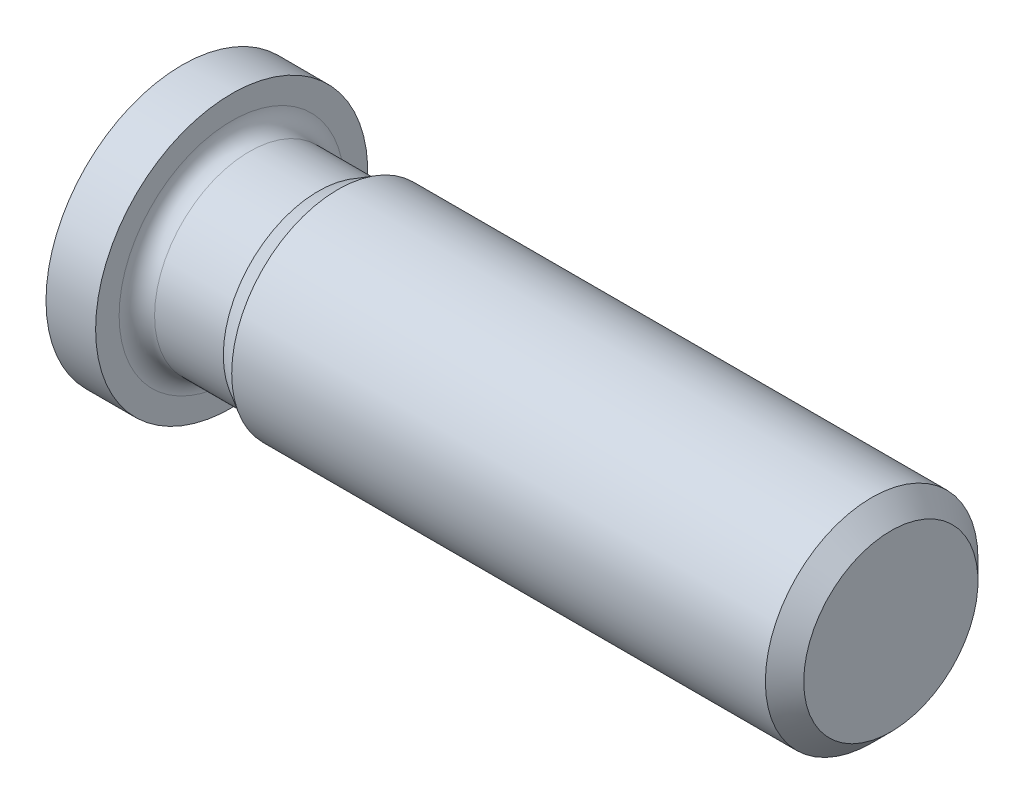
SolidWorks part; units mm, degrees
ref_plane "Front" through (0, 0, 0) normal (0, 0, 1) x (1, 0, 0)
ref_plane "Top" through (0, 0, 0) normal (0, 1, 0) x (1, 0, 0)
ref_plane "Right" through (0, 0, 0) normal (1, 0, 0) x (0, 0, -1)
sketch "Sketch1" plane through (0, 0, 0) normal (0, 0, 1) x (1, 0, 0)
  line L0 (0, 0) -> (22.7419, 0) construction
  line L1 (0, 0) -> (0, 0.44)
  line L2 (0, 0.44) -> (0.83, 0.9192)
  line L3 (0.83, 0.9192) -> (1.137, 3.84)
  line L4 (1.137, 3.84) -> (2.537, 3.84)
  line L5 (3.037, 3) -> (5.537, 3) construction
  line L6 (21.137, 3) -> (21.137, 0)
  line L7 (21.137, 0) -> (0, 0)
  line L8 (1.137, 3.84) -> (1.137, -8.0526) construction
  line L9 (2.537, 3.84) -> (2.537, 3.1765)
  line L10 (5.537, 3) -> (21.137, 3)
  line L11 (5.537, 3) -> (4.9767, 2.6765)
  line L12 (4.9767, 2.6765) -> (3.037, 2.6765)
  arc A0 (3.037, 2.6765) -> (2.537, 3.1765) centre (3.037, 3.1765) cw
  dimension "D5" = 0.5
  dimension "D3" = 6
  dimension "D4" = 30
  dimension "a" = 3
  dimension "d" = 6
  dimension "D6" = 5.353
revolve "Base" add sketch "Sketch1" angle 360 about L0
cosmetic thread "ThreadCosmetic1" [suppressed] parameters "D1"=15.6, "D2"=4.917
chamfer "EndChamfer" distance 0.5415 angle 45 1 edges at (21.137, 0, 3)
ref_plane "Plane1" through (4.037, 0, 0) normal (1, 0, 0) x (0, 0, -1)
sketch "Sketch2" plane through (0, 0, 0) normal (0, 0, 1) x (1, 0, 0)
  line L0 (20.5955, 2.531) -> (20.8662, 3)
  line L1 (20.8662, 3) -> (20.8662, 3.5)
  line L2 (20.8662, 3.5) -> (20.3247, 3.5)
  line L3 (20.3247, 3.5) -> (20.3247, 3)
  line L4 (20.3247, 3) -> (20.5955, 2.531)
  line L5 (0, 0) -> (22.4926, 0) construction
  line L7 (20.5955, 3) -> (20.5955, -3) construction
  dimension "D1" = 60
  dimension "D2" = 60
  dimension "D3" = 0.5
  dimension "D4" = 0.5415
  dimension "D5" = 6
revolve "Cut-Revolve10" [suppressed] cut sketch "Sketch2" angle 360 about L5
pattern_linear "LPattern10" [suppressed] count 24 spacing 0.6498 along (-1, 0, 0) of bodies 102
equation "\"D1@ThreadCosmetic1\" = \"l@Sketch1\" - \"h@Sketch1\" -\"a@Sketch1\""
equation "\"D1@EndChamfer\" =  ( \"d@Sketch1\" - \"D2@ThreadCosmetic1\" )  / 2"
equation "\"D5@Sketch2\" = \"d@Sketch1\""
equation "\"D4@Sketch2\" = (  \"d@Sketch1\" - \"D2@ThreadCosmetic1\" )  / 2"
equation "\"D3@LPattern10\" = \"D4@Sketch2\" * 1.2"
equation "\"D1@LPattern10\" = \"D1@ThreadCosmetic1\" / \"D3@LPattern10\""
